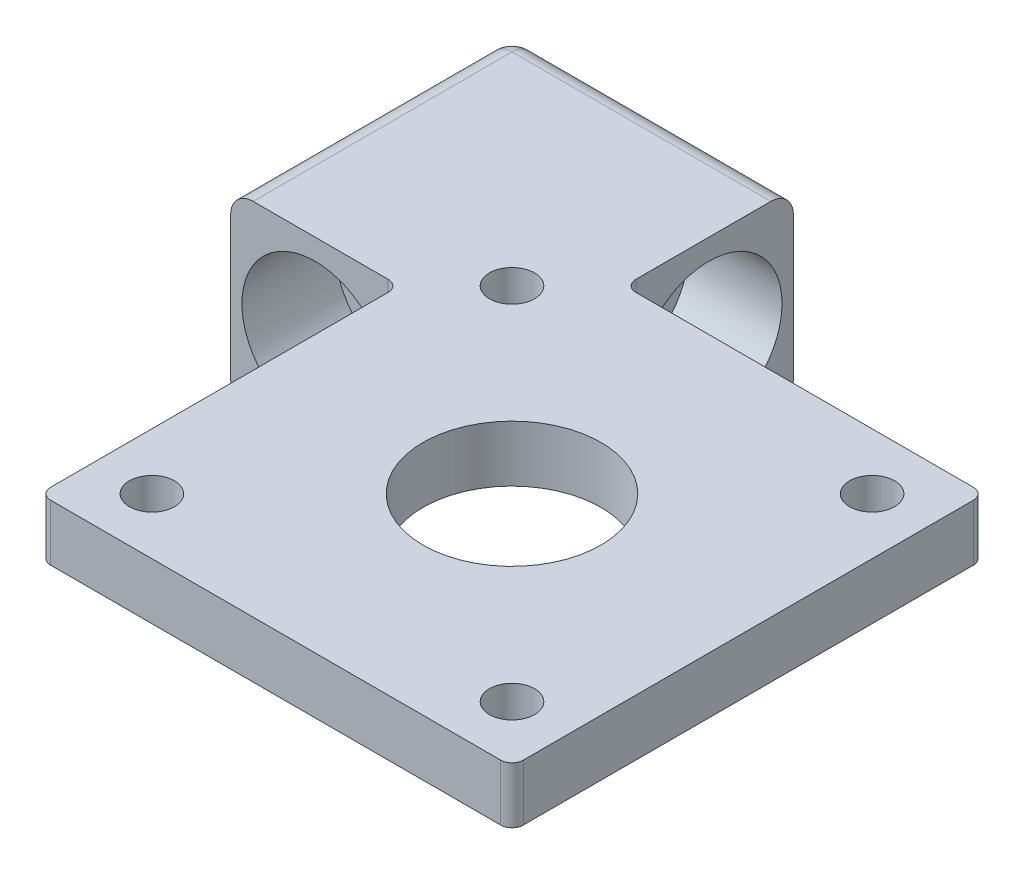
SolidWorks part; units mm, degrees
ref_plane "Front Plane" through (0, 0, 0) normal (0, 0, 1) x (1, 0, 0)
ref_plane "Top Plane" through (0, 0, 0) normal (0, 1, 0) x (1, 0, 0)
ref_plane "Right Plane" through (0, 0, 0) normal (1, 0, 0) x (0, 0, -1)
sketch "Sketch1" plane through (0, 0, 0) normal (0, 1, 0) x (1, 0, 0)
  line L1 (7.5, -5) -> (-7.5, -5)
  line L2 (7.5, -5) -> (7.5, 5)
  line L3 (7.5, 5) -> (-7.5, 5)
  line L4 (-7.5, -5) -> (-7.5, 5)
  line L5 (7.5, -5) -> (-7.5, 5) construction
  line L6 (7.5, 5) -> (-7.5, -5) construction
  line L8 (-7.5, 5) -> (-7.5, 20)
  line L9 (-7.5, 20) -> (7.5, 20)
  line L10 (7.5, 5) -> (7.5, 20)
  line L11 (7.5, 5) -> (17.5, 5)
  line L13 (7.5, 20) -> (17.5, 20)
  line L14 (17.5, 5) -> (17.5, 20)
  point P0 (0, 0)
  dimension "D1" = 10
  dimension "D2" = 15
  dimension "D3" = 15
  dimension "D4" = 10
extrude "Boss-Extrude1" add sketch "Sketch1" along normal blind 16.7 contours L4 L1 L2 L3 | L3 L10 L9 L8 | L11 L14 L13 L10 region at (0, 0, 0) region at (0, 0, -12.5) region at (12.5, 0, -12.5)
sketch "Sketch2" plane through (0, 0, 5) normal (0, 0, 1) x (1, 0, 0)
  line L0 (0, 0) -> (0, 16.7) construction
  line L1 (7.5, 0) -> (-7.5, 0) construction
  line L2 (7.5, 16.7) -> (-7.5, 16.7) construction
  circle A0 centre (0, 8.35) radius 6.5
  dimension "D1" = 13
extrude "Cut-Extrude1" cut sketch "Sketch2" against normal offset from surface (8.3 mm away) 16.7 up to face at (5, 8.35, -20)
sketch "Sketch3" plane through (17.5, 0, 0) normal (1, 0, 0) x (0, 0, -1)
  line L0 (12.5, 0) -> (12.5, 16.7) construction
  line L1 (5, 0) -> (20, 0) construction
  line L2 (5, 16.7) -> (20, 16.7) construction
  circle A0 centre (12.5, 8.35) radius 6.5
  dimension "D1" = 13
extrude "Cut-Extrude2" cut sketch "Sketch3" against normal offset from surface (8.3 mm away) 16.7 up to face at (-7.5, 8.35, -7.5)
sketch "Sketch4" plane through (0, 0, 0) normal (0, -1, 0) x (1, 0, 0)
  line L0 (0, 5) -> (0, -20) construction
  line L1 (7.5, 5) -> (-7.5, 5) construction
  line L2 (-7.5, -20) -> (17.5, -20) construction
  line L3 (17.5, -12.5) -> (-7.5, -12.5) construction
  line L4 (17.5, -5) -> (17.5, -20) construction
  line L5 (-7.5, 5) -> (-7.5, -20) construction
  circle A0 centre (0, -12.5) radius 6.5
  dimension "D1" = 13
extrude "Cut-Extrude3" cut sketch "Sketch4" against normal offset from surface (14.7 mm away) 2 up to face at (5.8333, 16.7, -6.6667)
fillet "Fillet8" radius 2 8 edges at (-7.5, 8.35, -20) (7.5, 8.35, -5) (-7.5, 0, -7.5) (-7.5, 16.7, -7.5) (7.5, 0, 0) (12.5, 0, -5) (5, 16.7, -20) (5, 0, -20)
sketch "Sketch5" plane through (0, 16.7, 0) normal (0, 1, 0) x (1, 0, 0)
  line L0 (12.5, -32) -> (12.5, 0)
  line L1 (7.5, -37) -> (49.5, -37)
  line L2 (7.5, -37) -> (7.5, 5)
  line L3 (7.5, 5) -> (49.5, 5)
  line L4 (49.5, -37) -> (49.5, 5)
  line L5 (44.5, 0) -> (12.5, 0)
  line L6 (7.5, -16) -> (49.5, -16) construction
  line L7 (28.5, 5) -> (28.5, -37) construction
  line L8 (44.5, -32) -> (12.5, -32)
  line L9 (44.5, -32) -> (44.5, 0)
  circle A0 centre (12.5, 0) radius 2
  circle A1 centre (12.5, -32) radius 2
  circle A2 centre (44.5, -32) radius 2
  circle A3 centre (44.5, 0) radius 2
  circle A4 centre (28.5, -16) radius 7.9065
  point P14 (28.5, 0)
  point P15 (12.5, -16)
  point P17 (28.5, -32)
  point P18 (44.5, -16)
  line M12 (7.5, -5) -> (7.5, 3)
  arc M13 (7.5, 3) -> (9.5, 5) centre (9.5, 3) cw
  line M14 (9.5, 5) -> (17.5, 5)
  dimension "D3" = 4
  dimension "D5" = 4
  dimension "D6" = 4
  dimension "D7" = 4
  dimension "D8" = 15.8129
  dimension "D1" = 42
  dimension "D2" = 42
  dimension "D4" = 32
extrude "Boss-Extrude3" add sketch "Sketch5" against normal blind 5 contours L1 L4 L3 L2 A3 L9 A2 L8 A1 L0 A0 L5 M14 M13 M12 | A3 L5 A0 L0 A1 L8 A2 L9 region at (12.9525, 16.7, 16) region at (8.094, 16.7, 21)
fillet "Fillet9" radius 1 5 edges at (7.5, 14.2, 5) (17.5, 14.2, -5) (7.5, 14.2, 37) (49.5, 14.2, 37) (49.5, 14.2, -5)
